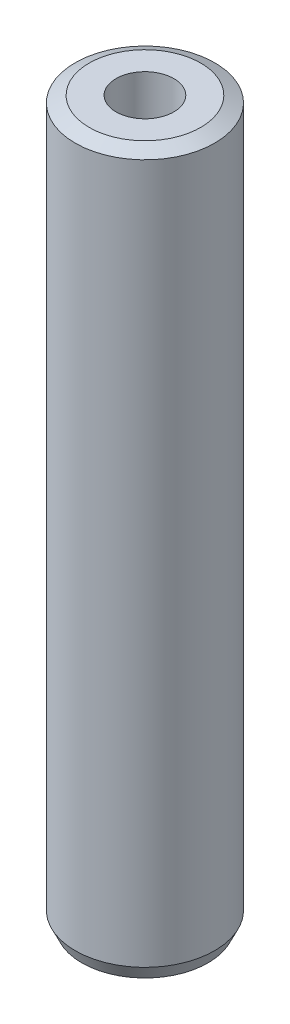
SolidWorks part; units mm, degrees
ref_plane "Front Plane" through (0, 0, 0) normal (0, 0, 1) x (1, 0, 0)
ref_plane "Top Plane" through (0, 0, 0) normal (0, 1, 0) x (1, 0, 0)
ref_plane "Right Plane" through (0, 0, 0) normal (1, 0, 0) x (0, 0, -1)
sketch "Sketch1" plane through (0, 0, 0) normal (0, 1, 0) x (1, 0, 0)
  circle A0 centre (0, 0) radius 35
  dimension "SHAFT_OD" = 70
extrude "Boss-Extrude1" add sketch "Sketch1" along normal blind 361.4224
sketch "Sketch2" plane through (0, 0, 0) normal (0, 1, 0) x (1, 0, 0)
  circle A0 centre (0, 0) radius 14.5099
  dimension "BORE_D" = 29.0198
extrude "Cut-Extrude1" cut sketch "Sketch2" along normal through all
chamfer "Chamfer1" distance 3.3378 angle 64.502 2 edges at (0, 361.4224, 35) (0, 0, 35) first distance on face at (0, 361.4224, 35) first distance on face at (0, 0, 14.5099)
